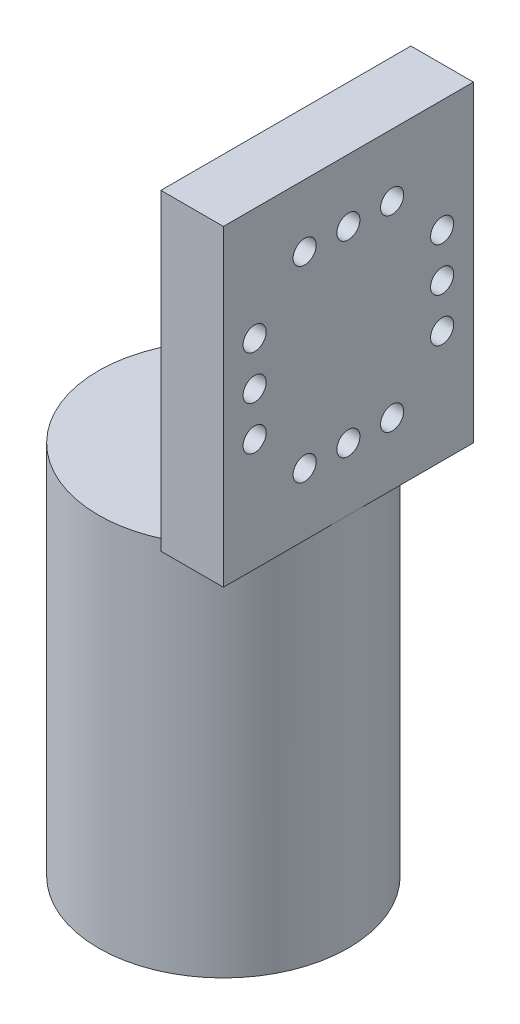
SolidWorks part; units mm, degrees
material "ABS"
ref_plane "Спереди" through (0, 0, 0) normal (0, 0, 1) x (1, 0, 0)
ref_plane "Сверху" through (0, 0, 0) normal (0, 1, 0) x (1, 0, 0)
ref_plane "Справа" through (0, 0, 0) normal (1, 0, 0) x (0, 0, -1)
sketch "Эскиз1" plane through (0, 0, 0) normal (0, 1, 0) x (1, 0, 0)
  line L0 (0, 0) -> (-10, 0) construction
  line L1 (-10, 0) -> (10, 0) construction
  line L2 (0, 0) -> (0, 10) construction
  line L3 (0, 10) -> (0, -10) construction
  line L9 (10, 0) -> (10, 10)
  line L10 (10, 0) -> (10, -10)
  line L11 (10, -10) -> (5, -10)
  line L12 (5, -10) -> (5, 10)
  line L13 (5, 10) -> (10, 10)
  circle A0 centre (0, 0) radius 10
  point P3 (9.9507, 10.0292)
  dimension "D1" = 10
  dimension "D2" = 20
  dimension "D3" = 5
extrude "Бобышка-Вытянуть1" add sketch "Эскиз1" against normal blind 30 contours A0
extrude "Бобышка-Вытянуть2" add sketch "Эскиз1<3>" along normal blind 25 contours A0 L9 L13 L12 | L12 A0 | A0 L12 L11 L10 region at (8.216, 0, -7.5598) region at (7.0502, 0, 0) region at (8.216, 0, 7.5598)
sketch "Эскиз1<3>" plane through (0, 0, 0) normal (0, 1, 0) x (1, 0, 0) same geometry as "Эскиз1"
sketch "Эскиз2" plane through (10, 0, 0) normal (1, 0, 0) x (0, 0, -1)
  line L0 (0, 0) -> (0, 25) construction
  line L1 (-10, 25) -> (10, 25) construction
  line L2 (-10, 0) -> (0, 0) construction
  line L3 (0, 5) -> (8.386, 5) construction
  line L4 (0, 5) -> (-7.1452, 5) construction
  line L5 (0, 12.5) -> (24.2139, 12.5) construction
  line L6 (0, 12.5) -> (-5.3984, 12.5) construction
  line L7 (-5.3984, 12.5) -> (-6.4218, 12.5) construction
  line L8 (0, 20) -> (10, 20) construction
  line L9 (10, 25) -> (10, 0) construction
  line L10 (0, 20) -> (-10, 20) construction
  line L11 (-10, 25) -> (-10, 0) construction
  line L12 (-7.5, 12.5) -> (-7.5, 21.4528) construction
  line L13 (-7.5, 21.4528) -> (-7.5, 5.5239) construction
  line L14 (7.5, 12.5) -> (7.5, 20.9865) construction
  line L15 (7.5, 20.9865) -> (7.5, 4.3624) construction
  circle A0 centre (0, 5) radius 0.925
  circle A1 centre (3.5, 5) radius 0.925
  circle A2 centre (-3.5, 5) radius 0.925
  circle A3 centre (0, 20) radius 0.925
  circle A4 centre (-3.5, 20) radius 0.925
  circle A5 centre (3.5, 20) radius 0.925
  circle A6 centre (-7.5, 12.5) radius 0.925
  circle A7 centre (7.5, 12.5) radius 0.925
  circle A8 centre (-7.5, 9) radius 0.925
  circle A9 centre (-7.5, 16) radius 0.925
  circle A10 centre (7.5, 9) radius 0.925
  circle A11 centre (7.5, 16) radius 0.925
  point P47 (0, 0)
  point P48 (0, 0)
  point P49 (0, 0)
  point P50 (0, 0)
  dimension "D1" = 1.85
  dimension "D6" = 1.85
  dimension "D2" = 5
  dimension "D3" = 3.5
  dimension "D4" = 3.5
  dimension "D5" = 7.5
  dimension "D7" = 7.5
  dimension "D8" = 3.5
  dimension "D9" = 3.5
  dimension "D10" = 7.5
  dimension "D11" = 7.5
  dimension "D12" = 3.5
  dimension "D13" = 3.5
  dimension "D14" = 3.5
  dimension "D15" = 3.5
extrude "Вырез-Вытянуть1" cut sketch "Эскиз2" against normal through all
sketch "Эскиз3" plane through (0, -30, 0) normal (0, -1, 0) x (1, 0, 0)
  circle A0 centre (0, 0) radius 5.05
  dimension "D1" = 10.1
extrude "Вырез-Вытянуть2" cut sketch "Эскиз3" against normal blind 25
